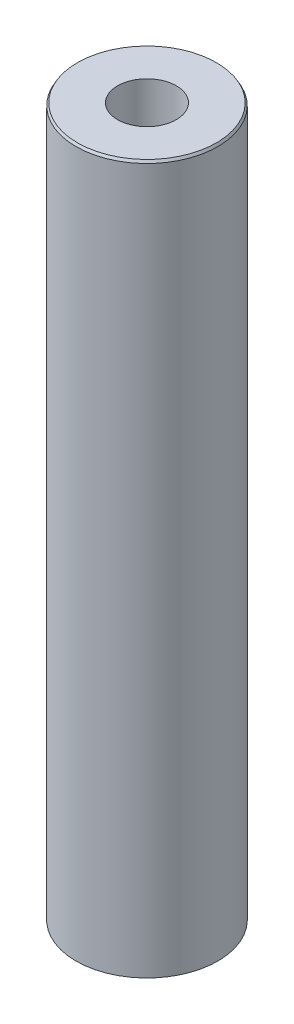
SolidWorks part; units mm, degrees
ref_plane "Front Plane" through (0, 0, 0) normal (0, 0, 1) x (1, 0, 0)
ref_plane "Top Plane" through (0, 0, 0) normal (0, 1, 0) x (1, 0, 0)
ref_plane "Right Plane" through (0, 0, 0) normal (1, 0, 0) x (0, 0, -1)
sketch "Sketch1" plane through (0, 0, 0) normal (0, 1, 0) x (1, 0, 0)
  circle A0 centre (0, 0) radius 60
  dimension "SHAFT_OD" = 120
extrude "Boss-Extrude1" add sketch "Sketch1" along normal blind 600
sketch "Sketch2" plane through (0, 0, 0) normal (0, 1, 0) x (1, 0, 0)
  circle A0 centre (0, 0) radius 24.8456
  dimension "BORE_D" = 49.6911
extrude "Cut-Extrude1" cut sketch "Sketch2" along normal through all
chamfer "Chamfer1" distance 2.1191 angle 30 2 edges at (0, 600, 60) (0, 0, 60) first distance on face at (0, 600, 60) first distance on face at (0, 0, 24.8456)
